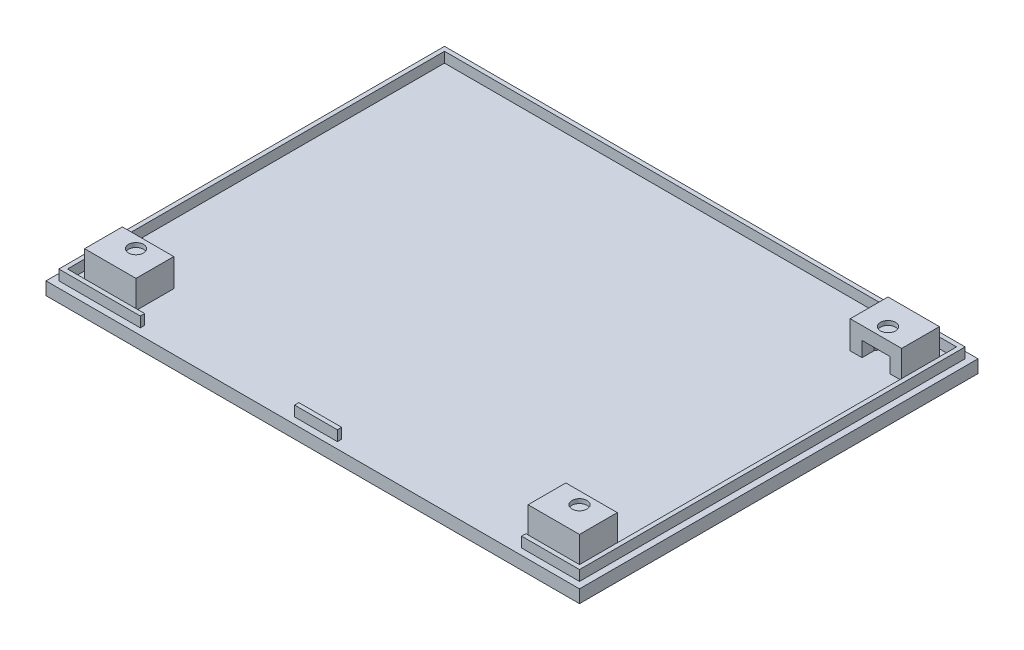
SolidWorks part; units mm, degrees
ref_plane "Спереди" through (0, 0, 0) normal (0, 0, 1) x (1, 0, 0)
ref_plane "Сверху" through (0, 0, 0) normal (0, 1, 0) x (1, 0, 0)
ref_plane "Справа" through (0, 0, 0) normal (1, 0, 0) x (0, 0, -1)
sketch "Эскиз1" plane through (0, 0, 0) normal (0, 1, 0) x (1, 0, 0)
  line L1 (-62.25, -46.5) -> (62.25, -46.5)
  line L2 (-62.25, -46.5) -> (-62.25, 46.5)
  line L3 (-62.25, 46.5) -> (62.25, 46.5)
  line L4 (62.25, -46.5) -> (62.25, 46.5)
  line L5 (-62.25, -46.5) -> (62.25, 46.5) construction
  line L6 (-62.25, 46.5) -> (62.25, -46.5) construction
  point P0 (0, 0)
  dimension "D1" = 124.5
  dimension "D2" = 93
extrude "Бобышка-Вытянуть1" add sketch "Эскиз1" along normal blind 3
sketch "Эскиз2" plane through (0, 3, 0) normal (0, 1, 0) x (1, 0, 0)
  line L2 (-60.25, -44.5) -> (-60.25, 44.5)
  line L3 (-60.25, 44.5) -> (60.25, 44.5)
  line L4 (60.25, -44.5) -> (60.25, 44.5)
  line L5 (-60.25, -44.5) -> (60.25, 44.5) construction
  line L6 (-60.25, 44.5) -> (60.25, -44.5) construction
  line L8 (-60.25, -44.5) -> (-41.75, -44.5)
  line L9 (60.25, -44.5) -> (47.25, -44.5)
  line L10 (-62.25, 46.5) -> (-62.25, -46.5) construction
  line L11 (-5.75, -44.5) -> (4.25, -44.5)
  line L12 (62.25, -46.5) -> (62.25, 46.5) construction
  point P0 (0, 0)
  dimension "D1" = 89
  dimension "D2" = 120.5
  dimension "D3" = 20.5
  dimension "D4" = 15
  dimension "D5" = 56.5
  dimension "D6" = 58
extrude "Вытянуть-Тонкостенный1" add sketch "Эскиз2" along normal blind 2.4 thin thin type mid plane wall 1
sketch "Эскиз3" plane through (0, 3, 0) normal (0, 1, 0) x (1, 0, 0)
  line L0 (-55, -36) -> (-55, -33.1854)
  line L5 (-57.75, -42) -> (57.75, -42) construction
  line L6 (-57.75, -42) -> (-57.75, 42) construction
  line L7 (-57.75, 42) -> (57.75, 42) construction
  line L8 (57.75, -42) -> (57.75, 42) construction
  line L9 (-51.75, -36) -> (51.75, -36) construction
  line L10 (-51.75, -36) -> (-51.75, 36) construction
  line L11 (-51.75, 36) -> (51.75, 36) construction
  line L12 (51.75, -36) -> (51.75, 36) construction
  line L13 (-51.75, -36) -> (51.75, 36) construction
  line L14 (-51.75, 36) -> (51.75, -36) construction
  line L15 (-57.75, -42) -> (57.75, 42) construction
  line L16 (-57.75, 42) -> (57.75, -42) construction
  line L17 (-48.5, -36) -> (-50.125, -33.1854) construction
  line L18 (-50.125, -33.1854) -> (-53.375, -33.1854) construction
  line L19 (-53.375, -33.1854) -> (-55, -36) construction
  line L20 (-55, -36) -> (-53.375, -38.8146)
  line L21 (-53.375, -38.8146) -> (-50.125, -38.8146)
  line L22 (-50.125, -38.8146) -> (-48.5, -36)
  line L23 (-55, -33.1854) -> (-57.75, -33.1854)
  line L24 (-57.75, -33.1854) -> (-57.75, -42)
  line L25 (-57.75, -42) -> (-45.75, -42)
  line L26 (-45.75, -42) -> (-45.75, -33.1854)
  line L27 (-48.5, -36) -> (-48.5, -33.1854)
  line L28 (-48.5, -33.1854) -> (-45.75, -33.1854)
  line L29 (55, 36) -> (55, 33.1854)
  line L30 (48.5, 36) -> (50.125, 33.1854) construction
  line L31 (50.125, 33.1854) -> (53.375, 33.1854) construction
  line L32 (53.375, 33.1854) -> (55, 36) construction
  line L33 (55, 36) -> (53.375, 38.8146)
  line L34 (53.375, 38.8146) -> (50.125, 38.8146)
  line L35 (50.125, 38.8146) -> (48.5, 36)
  line L36 (55, 33.1854) -> (57.75, 33.1854)
  line L37 (57.75, 33.1854) -> (57.75, 42)
  line L38 (57.75, 42) -> (45.75, 42)
  line L39 (45.75, 42) -> (45.75, 33.1854)
  line L40 (45.75, 33.1854) -> (48.5, 33.1854)
  line L41 (48.5, 33.1854) -> (48.5, 36)
  line L42 (55, -36) -> (55, -33.1854)
  line L43 (55, -36) -> (53.375, -33.1854) construction
  line L44 (53.375, -33.1854) -> (50.125, -33.1854) construction
  line L45 (50.125, -33.1854) -> (48.5, -36) construction
  line L46 (48.5, -36) -> (50.125, -38.8146)
  line L47 (50.125, -38.8146) -> (53.375, -38.8146)
  line L48 (53.375, -38.8146) -> (55, -36)
  line L49 (55, -33.1854) -> (57.75, -33.1854)
  line L50 (57.75, -33.1854) -> (57.75, -42)
  line L55 (48.5, -36) -> (48.5, -33.1854)
  line L56 (48.5, -33.1854) -> (45.75, -33.1854)
  line L57 (45.75, -33.1854) -> (45.75, -42)
  line L58 (45.75, -42) -> (57.75, -42)
  circle A0 centre (-51.75, -36) radius 2.8146 construction
  circle A1 centre (51.75, 36) radius 2.8146 construction
  circle A2 centre (51.75, -36) radius 2.8146 construction
  point P0 (0, 0)
  point P1 (0, 0)
  point P6 (0, 0)
  dimension "D1" = 115.5
  dimension "D2" = 84
  dimension "D3" = 103.5
  dimension "D4" = 72
  dimension "D5" = 6.5
  dimension "D6" = 2.75
  dimension "D7" = 6.5
  dimension "D8" = 2.75
  dimension "D9" = 6.5
  dimension "D10" = 2.75
extrude "Бобышка-Вытянуть2" add sketch "Эскиз3" along normal blind 3.5
sketch "Эскиз4" plane through (0, 6.5, 0) normal (0, 1, 0) x (1, 0, 0)
  line L0 (-57.75, -42) -> (-57.75, -33.1854)
  line L1 (-57.75, -33.1854) -> (-45.75, -33.1854)
  line L2 (-45.75, -33.1854) -> (-45.75, -42)
  line L3 (-45.75, -42) -> (-57.75, -42)
  line L4 (-55, -36) -> (-48.5, -36) construction
  line L5 (45.75, -33.1854) -> (57.75, -33.1854)
  line L6 (45.75, -33.1854) -> (45.75, -42)
  line L7 (45.75, -42) -> (57.75, -42)
  line L8 (57.75, -33.1854) -> (57.75, -42)
  line L9 (45.75, 42) -> (57.75, 42)
  line L10 (45.75, 42) -> (45.75, 33.1854)
  line L11 (45.75, 33.1854) -> (57.75, 33.1854)
  line L12 (57.75, 42) -> (57.75, 33.1854)
  line L13 (48.5, -36) -> (55, -36) construction
extrude "Бобышка-Вытянуть3" add sketch "Эскиз4" along normal blind 3
sketch "Эскиз5" plane through (0, 9.5, 0) normal (0, 1, 0) x (1, 0, 0)
  line L0 (45.75, 42) -> (45.75, 33.1854) construction
  line L1 (57.75, 42) -> (45.75, 42) construction
  line L2 (45.75, -42) -> (57.75, -42) construction
  line L3 (45.75, -33.1854) -> (45.75, -42) construction
  line L4 (-57.75, -42) -> (-45.75, -42) construction
  line L5 (-57.75, -33.1854) -> (-57.75, -42) construction
  circle A0 centre (-51.75, -36) radius 1.75
  circle A1 centre (51.75, -36) radius 1.75
  circle A2 centre (51.75, 36) radius 1.75
  dimension "D1" = 6
  dimension "D3" = 3.5
  dimension "D4" = 6
  dimension "D5" = 6
  dimension "D6" = 3.5
  dimension "D7" = 6
  dimension "D8" = 6
  dimension "D9" = 3.5
  dimension "D2" = 6
extrude "Вырез-Вытянуть1" cut sketch "Эскиз5" against normal blind 1
